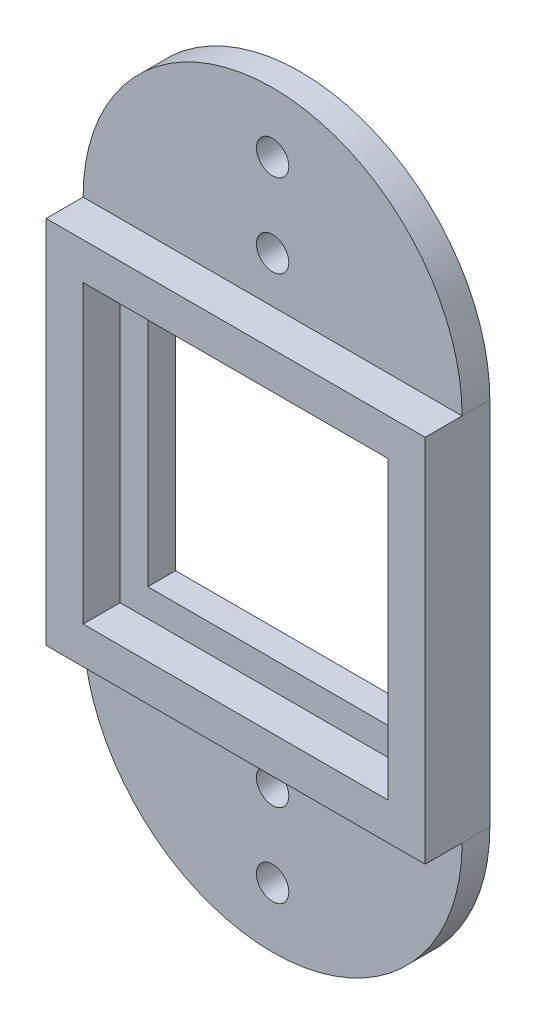
SolidWorks part; units mm, degrees
ref_plane "前视基准面" through (0, 0, 0) normal (0, 0, 1) x (1, 0, 0)
ref_plane "上视基准面" through (0, 0, 0) normal (0, 1, 0) x (1, 0, 0)
ref_plane "右视基准面" through (0, 0, 0) normal (1, 0, 0) x (0, 0, -1)
sketch "草图1" plane through (0, 0, 0) normal (0, 0, 1) x (1, 0, 0)
  line L0 (33, 16) -> (0, 16) construction
  line L1 (0, 32) -> (33, 32)
  line L2 (0, 32) -> (0, 0)
  line L3 (0, 0) -> (33, 0)
  line L4 (33, 32) -> (33, 0)
  line L5 (16.5, 0) -> (16.5, 32) construction
  line L7 (3, 3) -> (30, 3)
  line L8 (3, 3) -> (3, 29)
  line L9 (3, 29) -> (30, 29)
  line L10 (30, 3) -> (30, 29)
  line L11 (3, 3) -> (30, 29) construction
  line L12 (3, 29) -> (30, 3) construction
  line L13 (37, 36) -> (-4, 36)
  line L14 (37, 36) -> (37, -4)
  line L15 (37, -4) -> (-4, -4)
  line L16 (-4, 36) -> (-4, -4)
  line L17 (37, 36) -> (-4, -4) construction
  line L18 (37, -4) -> (-4, 36) construction
  circle A7 centre (16.5, 36) radius 20.5
  circle A8 centre (16.5, 41) radius 1.75
  circle A9 centre (16.5, 50) radius 1.75
  circle A10 centre (16.5, -4) radius 20.5
  circle A11 centre (16.5, -9) radius 1.75
  circle A12 centre (16.5, -18) radius 1.75
  point P9 (16.5, 16)
  point P14 (16.5, 16)
  dimension "D3" = 3
  dimension "D5" = 4
  dimension "D7" = 20.5
  dimension "D8" = 3.5
  dimension "D9" = 20.5
  dimension "D12" = 3.5
  dimension "D13" = 5
  dimension "D14" = 9
  dimension "D1" = 32
  dimension "D2" = 33
  dimension "D4" = 3
  dimension "D6" = 4
extrude "凸台-拉伸5" add sketch "草图1" along normal blind 7 contours L14 L13 L16 L15 | L2 L1 L4 L3
extrude "凸台-拉伸6" add sketch "草图1<7>" along normal blind 3 contours L2 L1 L4 L3 | L8 L7 L10 L9
sketch "草图1<7>" plane through (0, 0, 0) normal (0, 0, 1) x (1, 0, 0) same geometry as "草图1"
extrude "凸台-拉伸7" add sketch "草图1<9>" along normal blind 3 contours A10 L15 A11 A12 | L13 A7 A9 A8 region at (16.5, 44.6765, 0) region at (16.5, -12.6765, 0)
sketch "草图1<9>" plane through (0, 0, 0) normal (0, 0, 1) x (1, 0, 0) same geometry as "草图1"
